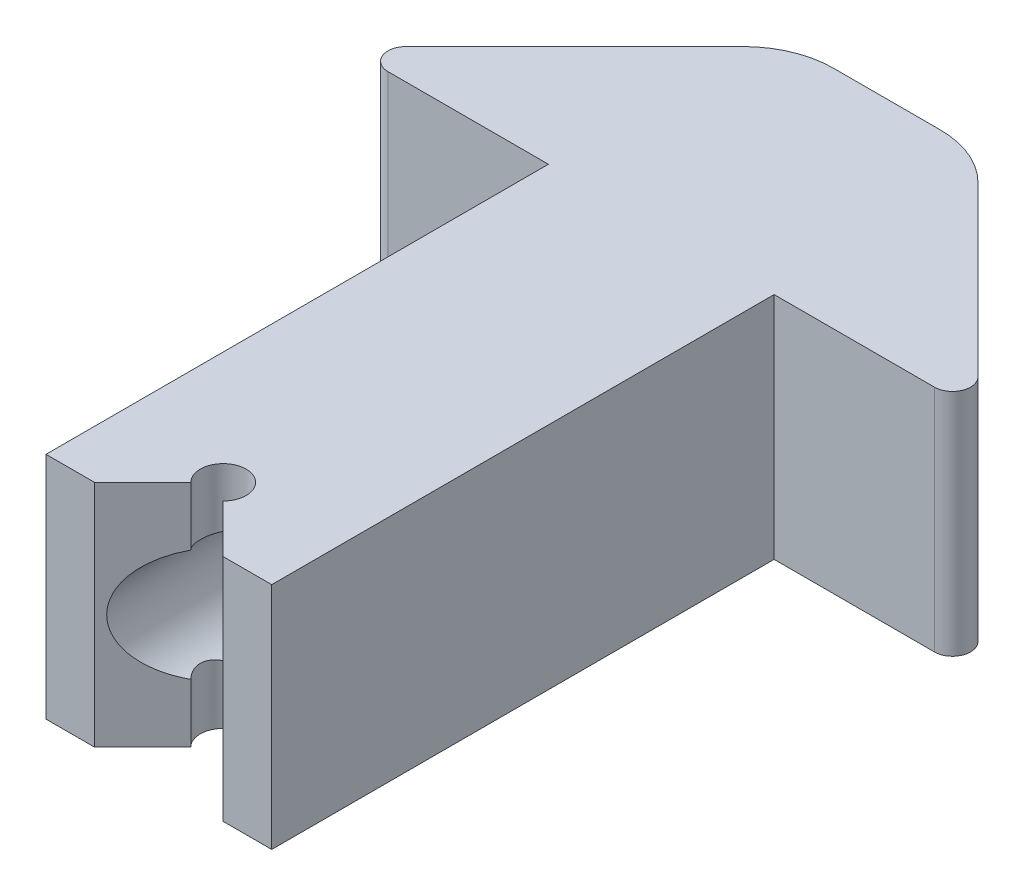
SolidWorks part; units mm, degrees
material "AISI 304"
ref_plane "Front Plane" through (0, 0, 0) normal (0, 0, 1) x (1, 0, 0)
ref_plane "Top Plane" through (0, 0, 0) normal (0, 1, 0) x (1, 0, 0)
ref_plane "Right Plane" through (0, 0, 0) normal (1, 0, 0) x (0, 0, -1)
sketch "Sketch1" plane through (0, 0, 0) normal (0, 1, 0) x (1, 0, 0)
  line L3 (0, 0) -> (4.1323, 0)
  line L4 (0, 0) -> (-2.0907, 0)
  line L5 (-2.0907, 0) -> (-2.0907, 0.889)
  line L6 (-2.0907, 0.889) -> (4.8943, 7.874)
  line L7 (4.8943, 7.874) -> (8.0693, 7.874)
  line L8 (8.0693, 7.874) -> (8.0693, -17.526)
  line L9 (4.1323, 0) -> (4.1323, -17.526)
  line L18 (4.1323, -17.526) -> (8.0693, -17.526)
  circle A1 centre (-1.4621, 0.6286) radius 0.6286
  point P4 (-1.2015, 0.9828)
  dimension "D1" = 3.937
  dimension "D2" = 7.874
  dimension "D3" = 10.16
  dimension "D4" = 135
  dimension "D6" = 3.175
  dimension "D7" = 25.4
extrude "Boss-Extrude1" add sketch "Sketch1" along normal blind 8.001 contours A1 L4 L3 L9 L18 L8 L7 L6 | A1 region at (5.3241, 0, 3.454) region at (-1.4621, 0, -0.6286)
ref_plane "Plane1" through (8.0693, 0, 0) normal (1, 0, 0) x (0, 0, -1)
mirror "Mirror1" about plane through (8.0693, 0, 0) normal (1, 0, 0) of "Boss-Extrude1"
sketch "Sketch4" plane through (0, 0, -7.874) normal (0, 0, -1) x (-1, 0, 0)
  line L2 (-8.0693, 0) -> (-8.0693, 8.001) construction
  line L5 (-4.8943, 0) -> (-11.2443, 0) construction
  line L6 (-4.8943, 8.001) -> (-11.2443, 8.001) construction
  circle A0 centre (-8.0693, 4.0005) radius 2.032
  point P4 (0, 0)
  point P5 (0, 0)
  dimension "D1" = 4.064
extrude "Cut-Extrude1" cut sketch "Sketch4" against normal blind 50.8
sketch "Sketch5" plane through (0, 0, -7.874) normal (0, 0, -1) x (-1, 0, 0)
  circle A0 centre (-8.0693, 4.0005) radius 3.048
  circle A1 centre (-8.0693, 4.0005) radius 2.032 construction
  dimension "D1" = 6.096
extrude "Cut-Extrude2" cut sketch "Sketch5" against normal blind 4.064
sketch "Sketch7" plane through (0, 8.001, 0) normal (0, 1, 0) x (1, 0, 0)
  line L0 (4.1323, -17.526) -> (12.0063, -17.526) construction
  line L1 (5.8243, -17.526) -> (10.3144, -17.526)
  line L2 (5.8243, -17.526) -> (8.0693, -15.2809)
  line L3 (8.0693, -15.2809) -> (10.3144, -17.526)
  circle A0 centre (8.0693, -15.2809) radius 0.8001
  point P7 (8.0693, -17.526)
  line M8 (4.1323, -17.526) -> (12.0063, -17.526)
  dimension "D2" = 1.6002
  dimension "D1" = 3.175
extrude "Cut-Extrude4" cut sketch "Sketch7" against normal through all contours L3 A0 L2 | L2 A0 L3 | A0 L2 L3 M8 region at (8.0693, 8.001, 16.8903) region at (8.0693, 8.001, 15.1209) region at (8.0693, 8.001, 15.7612)
fillet "Fillet2" radius 3.175 2 edges at (4.8943, 4.0005, -7.874) (11.2443, 4.0005, -7.874)
